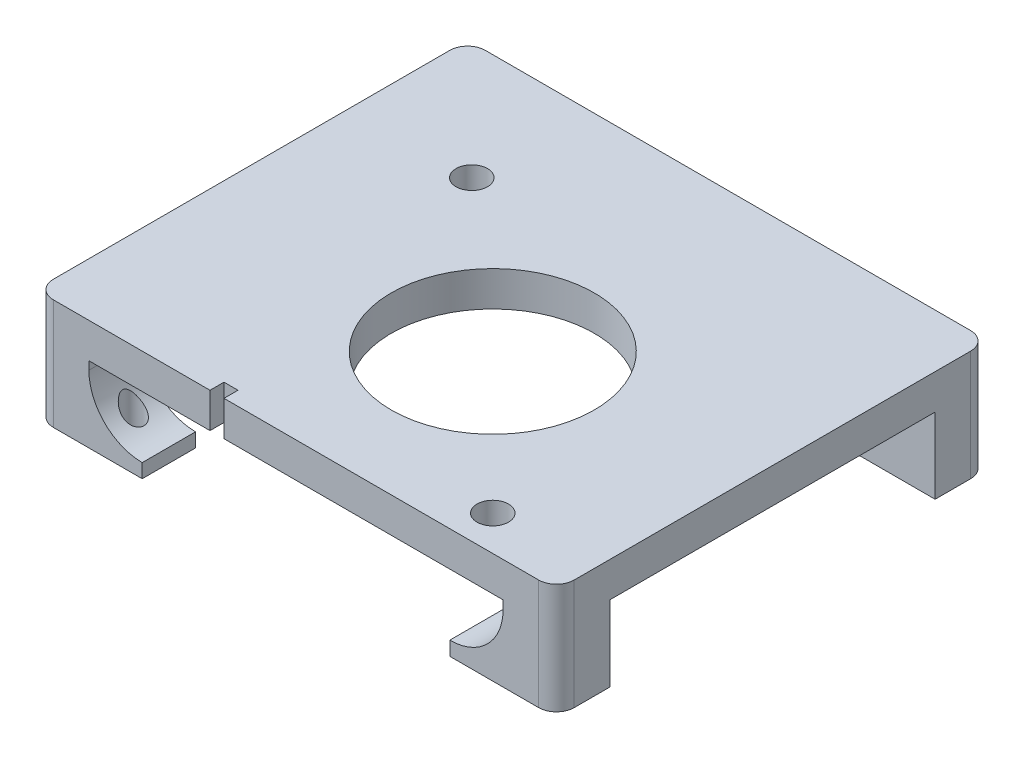
SolidWorks part; units mm, degrees
ref_plane "Front Plane" through (0, 0, 0) normal (0, 0, 1) x (1, 0, 0)
ref_plane "Top Plane" through (0, 0, 0) normal (0, 1, 0) x (1, 0, 0)
ref_plane "Right Plane" through (0, 0, 0) normal (1, 0, 0) x (0, 0, -1)
sketch "Sketch1" plane through (0, 0, 0) normal (0, 1, 0) x (1, 0, 0)
  line L0 (-26.8, -40.24) -> (0, -40.24) construction
  line L1 (-26.8, 25) -> (23.2, 25)
  line L2 (-26.8, 25) -> (-26.8, -25)
  line L3 (-26.8, -25) -> (23.2, -25)
  line L4 (23.2, 25) -> (23.2, -25)
  line L5 (-26.8, -25) -> (-40.324, -25)
  line L6 (-40.324, -25) -> (-40.324, 36.722)
  line L7 (-40.324, 36.722) -> (23.2, 36.722)
  line L8 (23.2, 36.722) -> (23.2, 25)
  line L10 (-15.4, -25) -> (-13.4, -25)
  line L11 (-15.4, -25) -> (-15.4, -23)
  line L12 (-15.4, -23) -> (-13.4, -23)
  line L13 (34.098, -25) -> (34.098, 36.722)
  line L14 (34.098, 36.722) -> (23.2, 36.722)
  line L15 (23.2, -25) -> (34.098, -25)
  line L16 (-13.4, -25) -> (-13.4, -23)
  circle A0 centre (0, 0) radius 14.5
  circle A1 centre (20, -20) radius 2.25
  circle A2 centre (-23, 20) radius 2.25
  point P16 (-13.4, -40.24)
  dimension "D1" = 4.5
  dimension "D2" = 29
  dimension "D5" = 20
  dimension "D3" = 20
  dimension "D4" = 23
  dimension "D6" = 50
  dimension "D7" = 20
  dimension "D8" = 50
  dimension "D9" = 26.8
  dimension "D10" = 25
  dimension "D11" = 15.24
  dimension "D12" = 61.722
  dimension "D13" = 26.924
  dimension "D14" = 2
  dimension "D15" = 74.422
  dimension "D16" = 2
extrude "Boss-Extrude1" add sketch "Sketch1" along normal blind 5 contours L8 L7 L6 L5 L2 L1 | L13 L14 L8 L4 | L3 L5 | L4 L1 L2 L3 A2 A1 A0 region at (-27.6857, 0, 0) region at (-1.8, 0, -24.2929) region at (28.649, 0, -5.861)
sketch "Sketch2" plane through (0, 0, 0) normal (0, -1, 0) x (1, 0, 0)
  line L0 (-40.324, 25) -> (-40.324, -36.722) construction
  line L1 (-40.324, 17.38) -> (-32.704, 17.38)
  line L2 (-40.324, 17.38) -> (-40.324, 25)
  line L3 (-40.324, 25) -> (-32.704, 25)
  line L4 (-32.704, 17.38) -> (-32.704, 25)
  line L5 (34.098, 25) -> (-13.4, 25) construction
  line L6 (34.098, 25) -> (34.098, -36.722) construction
  line L7 (26.478, 25) -> (34.098, 25)
  line L8 (26.478, 25) -> (26.478, 17.38)
  line L9 (26.478, 17.38) -> (34.098, 17.38)
  line L10 (34.098, 25) -> (34.098, 17.38)
  line L12 (34.098, -36.722) -> (26.478, -36.722)
  line L13 (34.098, -36.722) -> (34.098, -29.102)
  line L14 (34.098, -29.102) -> (26.478, -29.102)
  line L15 (26.478, -36.722) -> (26.478, -29.102)
  line L16 (-40.324, -36.722) -> (-32.704, -36.722)
  line L17 (-40.324, -36.722) -> (-40.324, -29.102)
  line L18 (-40.324, -29.102) -> (-32.704, -29.102)
  line L19 (-32.704, -36.722) -> (-32.704, -29.102)
  dimension "D1" = 7.62
extrude "Boss-Extrude2" add sketch "Sketch2" along normal blind 10.795
sketch "Sketch4" plane through (0, -10.795, 0) normal (0, -1, 0) x (1, 0, 0)
  line L1 (-32.704, 25) -> (-25.084, 25)
  line L2 (-32.704, 25) -> (-32.704, 17.38)
  line L3 (-32.704, 17.38) -> (-25.084, 17.38)
  line L4 (-25.084, 25) -> (-25.084, 17.38)
  line L5 (-32.704, -36.722) -> (-25.084, -36.722)
  line L6 (-32.704, -36.722) -> (-32.704, -29.102)
  line L7 (-32.704, -29.102) -> (-25.084, -29.102)
  line L8 (-25.084, -36.722) -> (-25.084, -29.102)
  line L9 (26.478, -36.722) -> (18.858, -36.722)
  line L10 (26.478, -36.722) -> (26.478, -29.102)
  line L11 (26.478, -29.102) -> (18.858, -29.102)
  line L12 (18.858, -36.722) -> (18.858, -29.102)
  line L13 (26.478, 25) -> (18.858, 25)
  line L14 (26.478, 25) -> (26.478, 17.38)
  line L15 (26.478, 17.38) -> (18.858, 17.38)
  line L16 (18.858, 25) -> (18.858, 17.38)
  circle A0 centre (-30.164, 21.19) radius 1.524
  circle A1 centre (23.938, 21.19) radius 1.524
  circle A2 centre (23.938, -32.912) radius 1.524
  circle A3 centre (-30.164, -32.912) radius 1.524
  point P28 (-25.084, -32.912)
  point P29 (-25.084, 21.19)
  dimension "D5" = 3.048
  dimension "D1" = 5.08
  dimension "D2" = 7.62
  dimension "D3" = 54.102
  dimension "D4" = 2.54
extrude "Boss-Extrude3" add sketch "Sketch4" against normal blind 2
sketch "Sketch5" plane through (0, 0, 25) normal (0, 0, 1) x (1, 0, 0)
  line L0 (-25.084, -8.795) -> (-32.704, -8.795) construction
  line L1 (-32.704, -8.795) -> (-32.704, 0) construction
  line L2 (-25.084, -8.795) -> (-32.704, -8.795)
  line L3 (-32.704, -8.795) -> (-32.704, -1.175)
  line L4 (-25.084, -10.795) -> (18.858, -10.795) construction
  line L5 (-3.113, -10.795) -> (-3.113, 0) construction
  line L6 (-13.4, 0) -> (26.478, 0) construction
  line L7 (18.858, -8.795) -> (26.478, -8.795)
  line L8 (26.478, -8.795) -> (26.478, -1.175)
  arc A0 (-32.704, -1.175) -> (-25.084, -8.795) centre (-25.084, -1.175) ccw
  arc A1 (26.478, -1.175) -> (18.858, -8.795) centre (18.858, -1.175) cw
extrude "Boss-Extrude4" add sketch "Sketch5" against normal up to vertex (7.62 mm away) up to point (-32.704, -8.795, 17.38)
sketch "Sketch6" plane through (0, 0, -36.722) normal (0, 0, -1) x (-1, 0, 0)
  line L0 (-26.478, -8.795) -> (-26.478, 0) construction
  line L1 (-18.858, -8.795) -> (-26.478, -8.795) construction
  line L2 (32.704, -8.795) -> (32.704, 0) construction
  line L3 (32.704, -8.795) -> (25.084, -8.795) construction
  line L4 (-26.478, -8.795) -> (-26.478, -1.175)
  line L5 (-18.858, -8.795) -> (-26.478, -8.795)
  line L6 (32.704, -8.795) -> (32.704, -1.175)
  line L7 (32.704, -8.795) -> (25.084, -8.795)
  arc A0 (-26.478, -1.175) -> (-18.858, -8.795) centre (-18.858, -1.175) ccw construction
  arc A1 (25.084, -8.795) -> (32.704, -1.175) centre (25.084, -1.175) ccw construction
  arc A2 (-26.478, -1.175) -> (-18.858, -8.795) centre (-18.858, -1.175) ccw
  arc A3 (25.084, -8.795) -> (32.704, -1.175) centre (25.084, -1.175) ccw
extrude "Boss-Extrude5" add sketch "Sketch6" against normal up to vertex (7.62 mm away) up to point (18.858, -8.795, -29.102)
extrude "Cut-Extrude1" cut sketch "Sketch4<2>" against normal up to vertex (10.795 mm away) contours A1 | A3 | A0 | A2 region at (-30.164, -10.795, 21.19) region at (23.938, -10.795, 21.19) region at (23.938, -10.795, -32.912) region at (-30.164, -10.795, -32.912) up to point (26.478, 0, -36.722)
sketch "Sketch4<2>" plane through (0, -10.795, 0) normal (0, -1, 0) x (1, 0, 0) same geometry as "Sketch4"
fillet "Fillet1" radius 2.54 4 edges at (-40.324, -2.8975, -36.722) (34.098, -2.8975, -36.722) (34.098, -2.8975, 25) (-40.324, -2.8975, 25)
